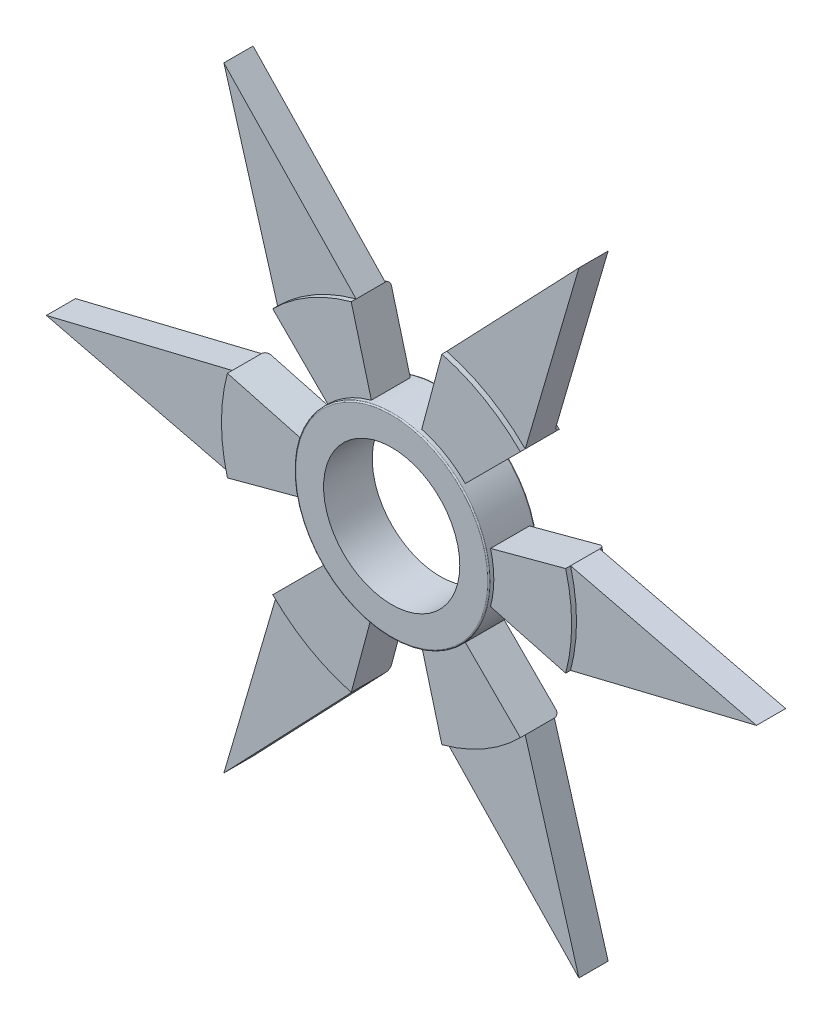
SolidWorks part; units mm, degrees
ref_plane "Front Plane" through (0, 0, 0) normal (0, 0, 1) x (1, 0, 0)
ref_plane "Top Plane" through (0, 0, 0) normal (0, 1, 0) x (1, 0, 0)
ref_plane "Right Plane" through (0, 0, 0) normal (1, 0, 0) x (0, 0, -1)
sketch "Sketch1" plane through (0, 0, 0) normal (0, 0, 1) x (1, 0, 0)
  line L0 (0, 0) -> (31905.7968, 0) construction
  line L1 (0, 0) -> (0, 31905.7968) construction
  line L2 (19.3185, 5.1764) -> (34.7733, 9.3175)
  line L3 (34.7733, 9.3175) -> (73, 0)
  line L4 (19.3185, -5.1764) -> (34.7733, -9.3175)
  line L5 (34.7733, -9.3175) -> (73, 0)
  line L6 (19.3185, 5.1764) -> (0, 0) construction
  line L7 (0, 0) -> (19.3185, -5.1764) construction
  line L8 (25.4558, -25.4558) -> (36.5, -63.2199)
  line L9 (5.1764, -19.3185) -> (9.3175, -34.7733)
  line L10 (14.1421, -14.1421) -> (25.4558, -25.4558)
  line L11 (9.3175, -34.7733) -> (36.5, -63.2199)
  line L12 (-9.3175, -34.7733) -> (-36.5, -63.2199)
  line L13 (-14.1421, -14.1421) -> (-25.4558, -25.4558)
  line L14 (-5.1764, -19.3185) -> (-9.3175, -34.7733)
  line L15 (-25.4558, -25.4558) -> (-36.5, -63.2199)
  line L16 (-34.7733, -9.3175) -> (-73, 0)
  line L17 (-19.3185, 5.1764) -> (-34.7733, 9.3175)
  line L18 (-19.3185, -5.1764) -> (-34.7733, -9.3175)
  line L19 (-34.7733, 9.3175) -> (-73, 0)
  line L20 (-25.4558, 25.4558) -> (-36.5, 63.2199)
  line L21 (-5.1764, 19.3185) -> (-9.3175, 34.7733)
  line L22 (-14.1421, 14.1421) -> (-25.4558, 25.4558)
  line L23 (-9.3175, 34.7733) -> (-36.5, 63.2199)
  line L24 (9.3175, 34.7733) -> (36.5, 63.2199)
  line L25 (14.1421, 14.1421) -> (25.4558, 25.4558)
  line L26 (5.1764, 19.3185) -> (9.3175, 34.7733)
  line L27 (25.4558, 25.4558) -> (36.5, 63.2199)
  circle A0 centre (0, 0) radius 14
  circle A1 centre (0, 0) radius 20
  arc A2 (25.4558, 25.4558) -> (9.3175, 34.7733) centre (0, 0) ccw
  circle A3 centre (0, 0) radius 73 construction
  arc A4 (-9.3175, 34.7733) -> (-25.4558, 25.4558) centre (0, 0) ccw
  arc A5 (-34.7733, 9.3175) -> (-34.7733, -9.3175) centre (0, 0) ccw
  arc A6 (-25.4558, -25.4558) -> (-9.3175, -34.7733) centre (0, 0) ccw
  arc A7 (9.3175, -34.7733) -> (25.4558, -25.4558) centre (0, 0) ccw
  arc A8 (34.7733, -9.3175) -> (34.7733, 9.3175) centre (0, 0) ccw
  point P15 (0, 0)
  point P43 (0, 0)
  dimension "D1" = 28
  dimension "D2" = 40
  dimension "D3" = 72
  dimension "D4" = 146
  dimension "D5" = 15
  dimension "D6" = 6
extrude "Boss-Extrude1" add sketch "Sketch1" along normal mid plane 10 contours A1 A0 region at (19.2681, 2.5367, 0)
extrude "Boss-Extrude2" add sketch "Sketch1<3>" along normal mid plane 8 contours L17 A5 L18 A1 | L21 A4 L22 A1 | L25 A2 L26 A1 | L4 A8 L2 A1 | L9 A7 L10 A1 | L13 A6 L14 A1 region at (28.4345, 0, 0) region at (14.2172, 24.625, 0) region at (14.2172, -24.625, 0) region at (-14.2172, 24.625, 0) region at (-14.2172, -24.625, 0) region at (-28.4345, 0, 0)
sketch "Sketch1<3>" plane through (0, 0, 0) normal (0, 0, 1) x (1, 0, 0) same geometry as "Sketch1"
extrude "Boss-Extrude3" add sketch "Sketch1<4>" along normal mid plane 6 contours A4 L23 L20 | A2 L27 L24 | A8 L5 L3 | A7 L11 L8 | A6 L15 L12 | A5 L19 L16 region at (48.0651, 0, 0) region at (24.0326, 41.6256, 0) region at (24.0326, -41.6256, 0) region at (-24.0326, 41.6256, 0) region at (-24.0326, -41.6256, 0) region at (-48.0651, 0, 0)
sketch "Sketch1<4>" plane through (0, 0, 0) normal (0, 0, 1) x (1, 0, 0) same geometry as "Sketch1"
fillet "Fillet1" radius 0.25 2 edges at (20, 0, 5) (20, 0, -5)
fillet "Fillet6" radius 1 6 edges at (18, 31.1769, -3) (36, 0, -4) (18, -31.1769, -4) (-18, -31.1769, -4) (-36, 0, -4) (-18, 31.1769, -4)
